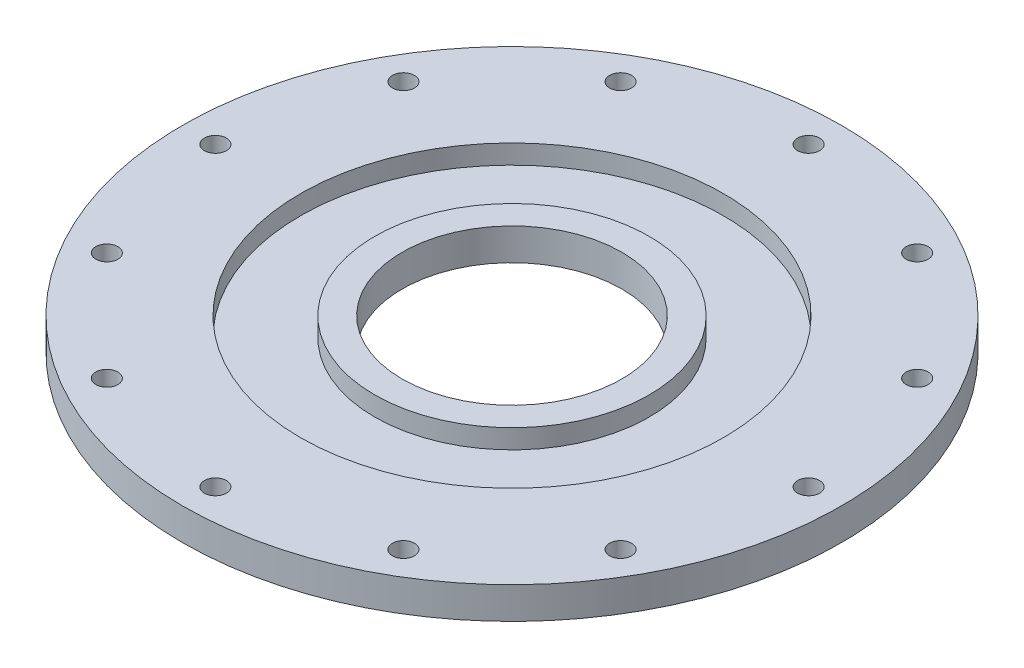
SolidWorks part; units mm, degrees
ref_plane "Front Plane" through (0, 0, 0) normal (0, 0, 1) x (1, 0, 0)
ref_plane "Top Plane" through (0, 0, 0) normal (0, 1, 0) x (1, 0, 0)
ref_plane "Right Plane" through (0, 0, 0) normal (1, 0, 0) x (0, 0, -1)
sketch "Sketch1" plane through (0, 0, 0) normal (0, 1, 0) x (1, 0, 0)
  circle A0 centre (0, 0) radius 60
  circle A1 centre (0, 0) radius 20
  dimension "D1" = 120
  dimension "D2" = 40
extrude "Boss-Extrude1" add sketch "Sketch1" along normal blind 5.8
sketch "Sketch2" plane through (0, 5.8, 0) normal (0, 1, 0) x (1, 0, 0)
  circle A0 centre (0, 0) radius 25
  circle A1 centre (0, 0) radius 38.5
  dimension "D1" = 50
  dimension "D2" = 77
extrude "Cut-Extrude1" cut sketch "Sketch2" against normal blind 3.5
sketch "Sketch3" plane through (0, 5.8, 0) normal (0, 1, 0) x (1, 0, 0)
  line L0 (0, 0) -> (27, 46.7654) construction
  line L1 (0, 0) -> (0, 54) construction
  circle A0 centre (0, 0) radius 54 construction
  circle A1 centre (0, 54) radius 2
  circle A2 centre (27, 46.7654) radius 2
  circle A3 centre (46.7654, 27) radius 2
  circle A4 centre (54, 0) radius 2
  circle A5 centre (46.7654, -27) radius 2
  circle A6 centre (27, -46.7654) radius 2
  circle A7 centre (0, -54) radius 2
  circle A8 centre (-27, -46.7654) radius 2
  circle A9 centre (-46.7654, -27) radius 2
  circle A10 centre (-54, 0) radius 2
  circle A11 centre (-46.7654, 27) radius 2
  circle A12 centre (-27, 46.7654) radius 2
  point P17 (0, 0)
  dimension "D1" = 108
  dimension "D2" = 4
  dimension "D4" = 30
  dimension "D3" = 12
extrude "Cut-Extrude2" cut sketch "Sketch3" against normal through all
